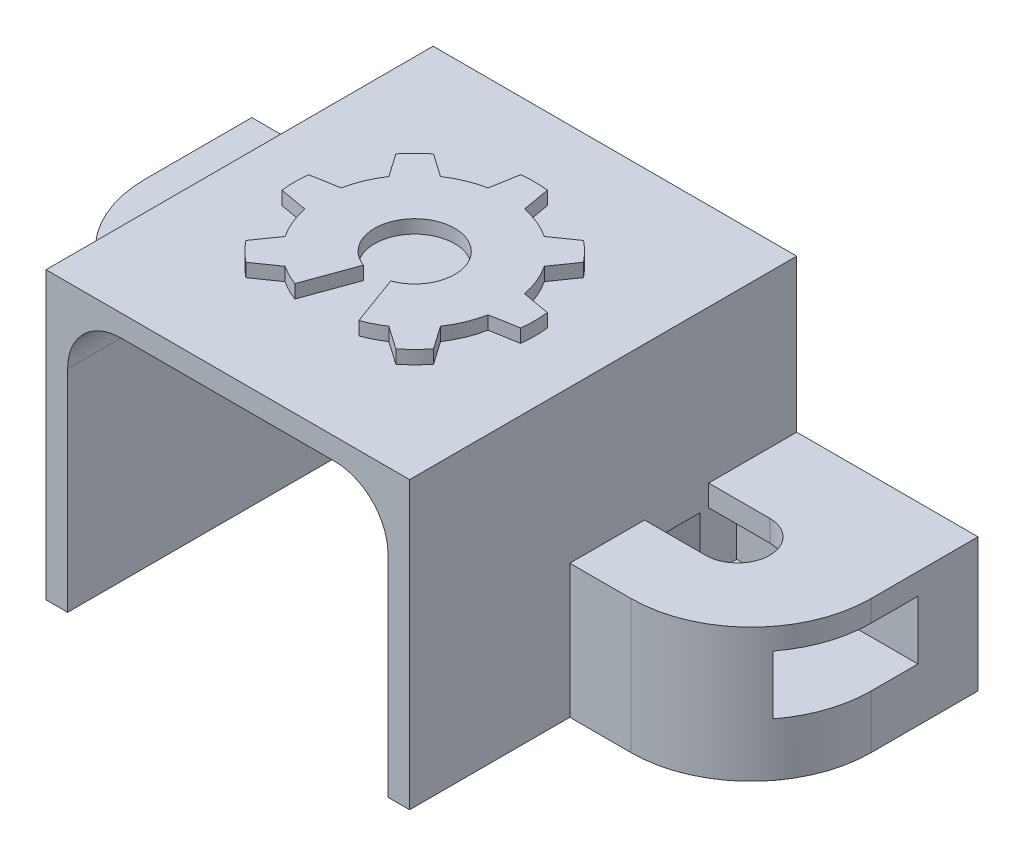
SolidWorks part; units mm, degrees
ref_plane "Front Plane" through (0, 0, 0) normal (0, 0, 1) x (1, 0, 0)
ref_plane "Top Plane" through (0, 0, 0) normal (0, 1, 0) x (1, 0, 0)
ref_plane "Right Plane" through (0, 0, 0) normal (1, 0, 0) x (0, 0, -1)
sketch "Sketch1" plane through (0, 0, 0) normal (0, 0, 1) x (1, 0, 0)
  line L0 (6, 0) -> (6, 9.9)
  line L1 (6, 9.9) -> (-6, 9.9)
  line L2 (0, 10.71) -> (0, 9.9) construction
  line L3 (-6.81, 10.71) -> (6.81, 10.71)
  line L4 (6.81, 10.71) -> (6.81, 0)
  line L5 (6.81, 0) -> (6, 0)
  line L6 (-6.81, 0) -> (-6, 0)
  line L7 (-6.81, 10.71) -> (-6.81, 0)
  line L8 (-6, 0) -> (-6, 9.9)
  dimension "D1" = 6
  dimension "D2" = 9.9
  dimension "D3" = 0.81
  dimension "D4" = 0.81
extrude "Boss-Extrude1" add sketch "Sketch1" along normal blind 5
fillet "Fillet2" radius 2 2 edges at (6, 9.9, 2.5) (-6, 9.9, 2.5)
sketch "Sketch3" plane through (0, 0, 0) normal (0, 0, -1) x (-1, 0, 0)
  line L0 (6, 0) -> (6, 9.75)
  line L1 (6, 9.75) -> (-6, 9.75)
  line L2 (-6.81, 10.71) -> (6.81, 10.71)
  line L3 (-6.81, 10.71) -> (6.81, 10.71) construction
  line L4 (6.81, 10.71) -> (6.81, 0)
  line L5 (6.81, 0) -> (6, 0)
  line L6 (0, 0) -> (0, 8.4964) construction
  line L7 (-5, 0) -> (5, 0) construction
  line L8 (-6.81, 0) -> (-6, 0)
  line L9 (-6.81, 10.71) -> (-6.81, 0)
  line L10 (-6, 0) -> (-6, 9.75)
  point P19 (0, 10.71)
  point P20 (0, 9.75)
  dimension "D1" = 9.75
extrude "Boss-Extrude3" add sketch "Sketch3" along normal blind 9.5
sketch "Sketch2" plane through (0, 0, 0) normal (0, 1, 0) x (1, 0, 0)
  line L0 (6.81, 9.5) -> (6.81, 6.2)
  line L1 (6.81, -5) -> (6.81, 9.5) construction
  line L2 (6.81, 1) -> (9.1, 1)
  line L3 (6.81, 9.5) -> (13.6, 9.5)
  line L4 (6.81, 6.2) -> (9.1, 6.2)
  line L5 (6.81, 3.8) -> (6.81, 1)
  line L6 (6.81, 3.8) -> (9.1, 3.8)
  line L7 (0, 0) -> (0, 14.4054) construction
  line L8 (-13.6, 9.5) -> (-13.6, 5.5)
  line L9 (-6.81, 9.5) -> (6.81, 9.5) construction
  line L10 (-6.81, 3.8) -> (-6.81, 1)
  line L11 (-6.81, 3.8) -> (-9.1, 3.8)
  line L12 (-6.81, 9.5) -> (-13.6, 9.5)
  line L13 (-6.81, 1) -> (-9.1, 1)
  line L14 (6.81, -5) -> (6.81, 9.5) construction
  line L15 (6.81, -5) -> (6.81, 9.5) construction
  line L16 (13.6, 9.5) -> (13.6, 5.5)
  line L17 (-6.81, 9.5) -> (-6.81, 6.2)
  line L18 (-6.81, 6.2) -> (-9.1, 6.2)
  arc A0 (13.6, 5.5) -> (9.1, 1) centre (9.1, 5.5) cw
  arc A1 (9.1, 6.2) -> (9.1, 3.8) centre (9.1, 5) cw
  arc A2 (-9.1, 6.2) -> (-9.1, 3.8) centre (-9.1, 5) ccw
  arc A3 (-13.6, 5.5) -> (-9.1, 1) centre (-9.1, 5.5) ccw
  dimension "D3" = 1.2
  dimension "D1" = 4.5
  dimension "D2" = 9.1
  dimension "D4" = 1
  dimension "D5" = 4.5
extrude "Boss-Extrude2" add sketch "Sketch2" along normal blind 5
fillet "Fillet1" [suppressed] radius 2
sketch "Sketch4" plane through (0, 0, 0) normal (0, 1, 0) x (1, 0, 0)
  line L0 (9.1, 5) -> (8.9, 5) construction
  line L1 (10.199, 7.25) -> (7.601, 7.25)
  line L2 (7.601, 7.25) -> (6.3019, 5)
  line L3 (6.3019, 5) -> (7.601, 2.75)
  line L4 (7.601, 2.75) -> (10.199, 2.75)
  line L5 (10.199, 2.75) -> (11.4981, 5)
  line L6 (11.4981, 5) -> (10.199, 7.25)
  circle A0 centre (8.9, 5) radius 2.25 construction
  arc A1 (9.1, 3.8) -> (9.1, 6.2) centre (9.1, 5) ccw construction
  dimension "D1" = 4.5
  dimension "D2" = 0.2
extrude "Cut-Extrude1" cut sketch "Sketch4" along normal blind 2.2 from offset 2
mirror "Mirror2" about plane through (0, 0, 0) normal (1, 0, 0) of "Cut-Extrude1"
mirror "Mirror1" [suppressed] about plane through (0, 0, 0) normal (1, 0, 0)
sketch "Sketch5" plane through (0, 0, -9.5) normal (0, 0, -1) x (-1, 0, 0)
  line L0 (-7, 0) -> (-7, -0.06)
  line L1 (-6.25, -0.81) -> (6.25, -0.81)
  line L2 (7, -0.06) -> (7, 0)
  line L3 (-6, 0) -> (-6, -0.45)
  line L4 (-6, -0.45) -> (0, -0.45)
  line L5 (0, -0.45) -> (6, -0.45)
  line L6 (6, -0.45) -> (6, 0)
  line L8 (6, 0) -> (7, 0)
  line L9 (-6, 0) -> (-7, 0)
  line L10 (-6, 9.75) -> (-4.7599, 9.75) construction
  arc A0 (6.25, -0.81) -> (7, -0.06) centre (6.25, -0.06) ccw
  arc A1 (-7, -0.06) -> (-6.25, -0.81) centre (-6.25, -0.06) ccw
  point P2 (-6, 0)
  point P6 (6, 0)
  dimension "D2" = 0.75
  dimension "D1" = 10.2
  dimension "D3" = 14
  dimension "D4" = 7
extrude "Boss-Extrude4" [suppressed] add sketch "Sketch5" against normal blind 2.5
chamfer "Chamfer1" [suppressed] distance 1 angle 45
sketch "Sketch6" plane through (0, 10.71, 0) normal (0, 1, 0) x (1, 0, 0)
  line L0 (0.513, 0.5905) -> (1.1971, -1.2889)
  line L1 (-0.513, 0.5905) -> (-1.1971, -1.2889)
  line L2 (0, 0) -> (0, 2) construction
  line L3 (1.9441, -0.9104) -> (2.8087, -1.5158)
  line L4 (2.9104, 0.0559) -> (3.5158, -0.8087)
  line L5 (0, 2) -> (3.182, -1.182) construction
  line L6 (0.6833, -1.4327) -> (0.5, -2.4721) [skipped]
  line L7 (-0.6833, -1.4327) -> (-0.5, -2.4721) [skipped]
  line L8 (-1.9441, -0.9104) -> (-2.8087, -1.5158)
  line L9 (-2.9104, 0.0559) -> (-3.5158, -0.8087)
  line L10 (-3.4327, 1.3167) -> (-4.4721, 1.5)
  line L11 (-3.4327, 2.6833) -> (-4.4721, 2.5)
  line L12 (-2.9104, 3.9441) -> (-3.5158, 4.8087)
  line L13 (-1.9441, 4.9104) -> (-2.8087, 5.5158)
  line L14 (-0.6833, 5.4327) -> (-0.5, 6.4721)
  line L15 (0.6833, 5.4327) -> (0.5, 6.4721)
  line L16 (1.9441, 4.9104) -> (2.8087, 5.5158)
  line L17 (2.9104, 3.9441) -> (3.5158, 4.8087)
  line L18 (3.4327, 2.6833) -> (4.4721, 2.5)
  line L19 (3.4327, 1.3167) -> (4.4721, 1.5)
  arc A0 (0.513, 0.5905) -> (-0.513, 0.5905) centre (0, 2) ccw
  arc A1 (3.5158, -0.8087) -> (2.8087, -1.5158) centre (0, 2) cw
  arc A2 (-1.1971, -1.2889) -> (-1.9441, -0.9104) centre (0, 2) cw
  arc A3 (0.5, -2.4721) -> (-0.5, -2.4721) centre (0, 2) cw [skipped]
  arc A4 (-2.8087, -1.5158) -> (-3.5158, -0.8087) centre (0, 2) cw
  arc A5 (-4.4721, 1.5) -> (-4.4721, 2.5) centre (0, 2) cw
  arc A6 (-3.5158, 4.8087) -> (-2.8087, 5.5158) centre (0, 2) cw
  arc A7 (-0.5, 6.4721) -> (0.5, 6.4721) centre (0, 2) cw
  arc A8 (2.8087, 5.5158) -> (3.5158, 4.8087) centre (0, 2) cw
  arc A9 (4.4721, 2.5) -> (4.4721, 1.5) centre (0, 2) cw
  arc A10 (-2.9104, 0.0559) -> (-3.4327, 1.3167) centre (0, 2) cw
  arc A11 (-3.4327, 2.6833) -> (-2.9104, 3.9441) centre (0, 2) cw
  arc A12 (-1.9441, 4.9104) -> (-0.6833, 5.4327) centre (0, 2) cw
  arc A13 (0.6833, 5.4327) -> (1.9441, 4.9104) centre (0, 2) cw
  arc A14 (2.9104, 3.9441) -> (3.4327, 2.6833) centre (0, 2) cw
  arc A15 (3.4327, 1.3167) -> (2.9104, 0.0559) centre (0, 2) cw
  arc A16 (1.9441, -0.9104) -> (1.1971, -1.2889) centre (0, 2) cw
  point P44 (0, 2)
  dimension "D1" = 1.5
  dimension "D2" = 3.5
  dimension "D3" = 4.5
  dimension "D7" = 1
  dimension "D4" = 20
  dimension "D5" = 20
  dimension "D6" = 10
  dimension "D8" = 45
  dimension "D10" = 2
  dimension "D9" = 8
extrude "Boss-Extrude5" add sketch "Sketch6" along normal blind 0.5
sketch "Sketch7" plane through (13.6, 0, 0) normal (1, 0, 0) x (0, 0, -1)
  line L0 (5.5, 0) -> (9.5, 0) construction
  line L1 (2.75, 4.2) -> (7.25, 4.2)
  line L2 (2.75, 4.2) -> (2.75, 2)
  line L3 (2.75, 2) -> (7.25, 2)
  line L4 (7.25, 4.2) -> (7.25, 2)
  line L5 (3.8, 1.9716) -> (6.2, 1.9716) construction
  line L7 (3.8, 2) -> (3.8, 4.2) construction
  line L8 (6.2, 1.9716) -> (5, 1.9716) construction
  line L9 (5, 1.9716) -> (5, 4.2) construction
  line L10 (6.2, 4.2) -> (6.2, 2) construction
  dimension "D1" = 4.5
  dimension "D2" = 2.2
  dimension "D3" = 2
extrude "Cut-Extrude3" cut sketch "Sketch7" against normal up to surface (6.79 mm away) up to face at (6.81, 3.1, -5)
sketch "Sketch8" plane through (-13.6, 0, 0) normal (-1, 0, 0) x (0, 0, 1)
  line L4 (-2.75, 4.2) -> (-7.25, 4.2)
  line L5 (-7.25, 4.2) -> (-7.25, 2)
  line L6 (-7.25, 2) -> (-2.75, 2)
  line L7 (-2.75, 2) -> (-2.75, 4.2)
  line L8 (-2.75, 4.2) -> (-7.25, 4.2)
  line L9 (-7.25, 4.2) -> (-7.25, 2)
  line L10 (-7.25, 2) -> (-2.75, 2)
  line L11 (-2.75, 2) -> (-2.75, 4.2)
  dimension "D1" = 0
extrude "Cut-Extrude4" cut sketch "Sketch8" against normal up to surface (6.79 mm away) up to face at (-6.81, 3.1, -5)
